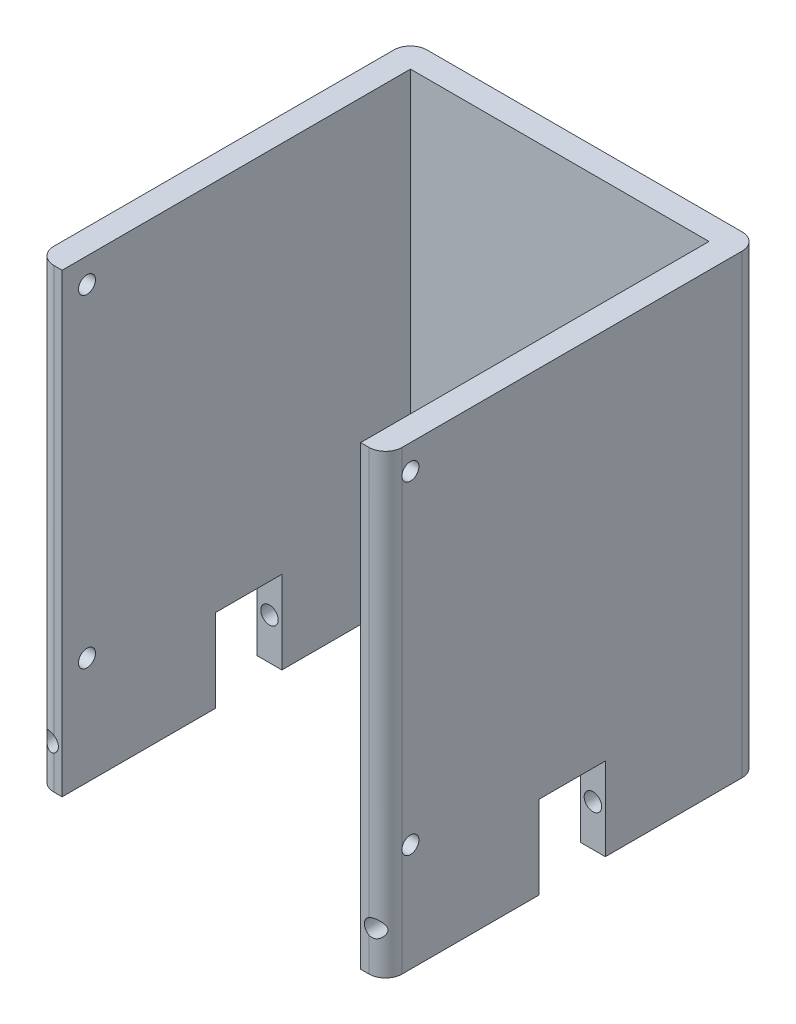
SolidWorks part; units mm, degrees
ref_plane "前基準面" through (0, 0, 0) normal (0, 0, 1) x (1, 0, 0)
ref_plane "上基準面" through (0, 0, 0) normal (0, 1, 0) x (1, 0, 0)
ref_plane "右基準面" through (0, 0, 0) normal (1, 0, 0) x (0, 0, -1)
sketch "草圖1" plane through (0, 0, 0) normal (0, 0, 1) x (1, 0, 0)
  line L0 (-14.5455, -28.0909) -> (-15.5455, -28.0909)
  line L1 (-14.5455, 16.9091) -> (25.4545, 16.9091)
  line L3 (-14.5455, -28.0909) -> (25.4545, -28.0909)
  line L5 (-15.5455, -28.0909) -> (-15.5455, 16.9091)
  line L6 (-15.5455, 16.9091) -> (-14.5455, 16.9091)
  line L8 (26.4545, -28.0909) -> (26.4545, 16.9091)
  line L9 (26.4545, 16.9091) -> (25.4545, 16.9091)
  line L10 (26.4545, -28.0909) -> (25.4545, -28.0909)
  dimension "D1" = 40
  dimension "D2" = 45
  dimension "D3" = 1
  dimension "D4" = 1
extrude "填料-伸長1" add sketch "草圖1" along normal blind 40 and the other way blind 5 contours L3 L10 L8 L9 L1 L6 L5 L0
sketch "草圖2" plane through (0, 16.9091, 0) normal (0, 1, 0) x (1, 0, 0)
  line L0 (5.4545, 5) -> (5.4545, -40.6532) construction
  line L1 (-15.5455, 5) -> (26.4545, 5) construction
  line L2 (-15.5455, -40) -> (26.4545, -40) construction
  line L3 (-12.5455, -3) -> (23.4545, -3)
  line L4 (-12.5455, -3) -> (-12.5455, -40)
  line L5 (-12.5455, -40) -> (23.4545, -40)
  line L6 (23.4545, -3) -> (23.4545, -40)
  dimension "D3" = 37
extrude "除料-伸長1" cut sketch "草圖2" against normal blind 50
sketch "草圖5" plane through (0, 16.9091, 0) normal (0, 1, 0) x (1, 0, 0)
  line L1 (-12.5455, -3) -> (23.4545, -3)
  line L2 (-12.5455, -3) -> (-12.5455, 2)
  line L3 (-12.5455, 2) -> (23.4545, 2)
  line L4 (23.4545, -3) -> (23.4545, 2)
  dimension "D1" = 36
  dimension "D2" = 5
extrude "除料-伸長4" cut sketch "草圖5" against normal blind 43
ref_plane "平面1" through (0, 16.9091, 0) normal (0, 1, 0) x (1, 0, 0)
ref_plane "平面2" through (0, -28.0909, 0) normal (0, -1, 0) x (-1, 0, 0)
ref_plane "平面4" through (-15.5455, 0, 0) normal (-1, 0, 0) x (0, 0, 1)
sketch "草圖9" plane through (-15.5455, 0, 0) normal (-1, 0, 0) x (0, 0, 1)
  line L3 (-5, -28.0909) -> (40, -28.0909) construction
  line L4 (40, -28.0909) -> (40, 16.9091) construction
  line L5 (-5, 16.9091) -> (40, 16.9091) construction
  circle A2 centre (37, -25.0909) radius 1.025
  circle A3 centre (37, 13.9091) radius 1.025
  dimension "D1" = 2.05
  dimension "D2" = 2.05
  dimension "D3" = 3
  dimension "D4" = 3
  dimension "D5" = 3
  dimension "D6" = 3
extrude "除料-伸長5" cut sketch "草圖9" against normal blind 45.5
sketch "草圖10" plane through (0, 16.9091, 0) normal (0, 1, 0) x (1, 0, 0)
  line L0 (5.4545, -3) -> (5.4545, 10.5844) construction
  line L1 (-12.5455, -3) -> (23.4545, -3) construction
  line L5 (-15.5455, -17.5) -> (26.4545, -17.5) construction
  line L6 (-15.5455, 22.55) -> (-15.5455, -22.55) construction
  line L7 (26.4545, 5) -> (26.4545, -40) construction
  line L8 (-15.5455, 5) -> (26.4545, 5) construction
  line L10 (-12.5455, 2) -> (-12.5455, -40) construction
  line L11 (-15.5455, -13.5) -> (-12.5455, -13.5)
  line L12 (-15.5455, -13.5) -> (-15.5455, -21.5)
  line L13 (-15.5455, -21.5) -> (-12.5455, -21.5)
  line L14 (-12.5455, -13.5) -> (-12.5455, -21.5)
  line L15 (26.4545, -21.5) -> (23.4545, -21.5)
  line L16 (23.4545, -13.5) -> (23.4545, -21.5)
  line L17 (26.4545, -13.5) -> (23.4545, -13.5)
  line L18 (26.4545, -13.5) -> (26.4545, -21.5)
  dimension "D1" = 22.5
  dimension "D2" = 4
  dimension "D3" = 3
  dimension "D4" = 4
sketch "草圖11" plane through (0, -28.0909, 0) normal (0, -1, 0) x (-1, 0, 0)
  line L0 (-26.4545, -17.5) -> (15.8441, -17.5) construction
  line L1 (-26.4545, 5) -> (-26.4545, -40) construction
  line L2 (-26.4545, 5) -> (15.5455, 5) construction
  line L3 (-5.4545, 5) -> (-5.4545, -41.7705) construction
  line L4 (-26.4545, -40) -> (-23.4545, -40)
  line L5 (-26.4545, -13.5) -> (-23.4545, -13.5)
  line L6 (-26.4545, -13.5) -> (-26.4545, 5)
  line L7 (-26.4545, 5) -> (-23.4545, 5)
  line L8 (-23.4545, -13.5) -> (-23.4545, 5)
  line L9 (-23.4545, -21.5) -> (-23.4545, -40)
  line L10 (-26.4545, -21.5) -> (-23.4545, -21.5)
  line L11 (-26.4545, -21.5) -> (-26.4545, -40)
  line L12 (15.5455, -21.5) -> (15.5455, -40)
  line L13 (15.5455, -21.5) -> (12.5455, -21.5)
  line L14 (12.5455, -21.5) -> (12.5455, -40)
  line L15 (15.5455, -40) -> (12.5455, -40)
  line L16 (15.5455, 5) -> (12.5455, 5)
  line L17 (12.5455, -13.5) -> (12.5455, 5)
  line L18 (15.5455, -13.5) -> (12.5455, -13.5)
  line L19 (15.5455, -13.5) -> (15.5455, 5)
  dimension "D1" = 22.5
  dimension "D2" = 21
  dimension "D3" = 3
  dimension "D4" = 4
extrude "填料-伸長5" add sketch "草圖11" along normal blind 10
ref_plane "平面6" through (0, 0, -5) normal (0, 0, -1) x (-1, 0, 0)
sketch "草圖13" plane through (0, 0, -5) normal (0, 0, -1) x (-1, 0, 0)
  line L0 (-26.4545, -33.0909) -> (15.5455, -33.0909) construction
  line L1 (-26.4545, -38.0909) -> (-26.4545, 16.9091) construction
  line L2 (15.5455, -24.75) -> (15.5455, 24.75) construction
  line L3 (-24.9545, -38.0909) -> (-24.9545, -17.409) construction
  line L4 (-23.4545, -38.0909) -> (-26.4545, -38.0909) construction
  line L5 (-5.4545, -33.0909) -> (-5.4545, 7.1098) construction
  circle A0 centre (-24.9545, -33.0909) radius 1.05
  circle A1 centre (14.0455, -33.0909) radius 1.05
  dimension "D2" = 2.1
  dimension "D1" = 5
extrude "除料-伸長7" cut sketch "草圖13" against normal blind 63.5
fillet "圓角4" radius 2 1 edges at (26.4545, -10.5909, -5)
fillet "圓角5" radius 2 1 edges at (-15.5455, -10.5909, -5)
fillet "圓角6" radius 2 1 edges at (26.4545, -10.5909, 40)
fillet "圓角7" radius 2 1 edges at (-15.5455, -10.5909, 40)
